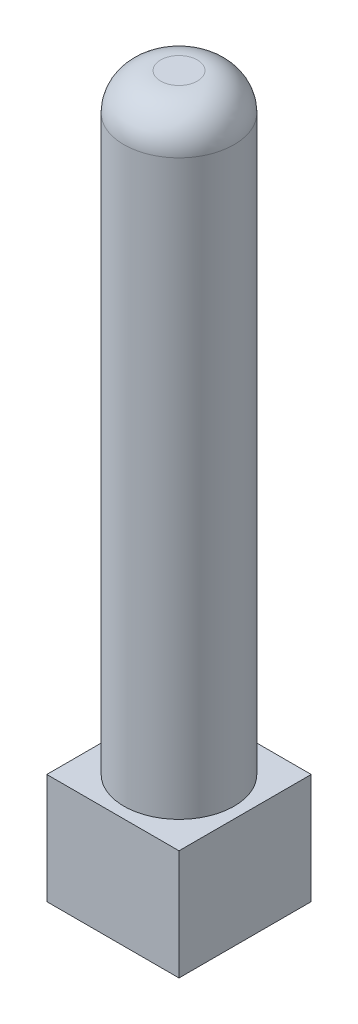
SolidWorks part; units mm, degrees
ref_plane "Plan de face" through (0, 0, 0) normal (0, 0, 1) x (1, 0, 0)
ref_plane "Plan de dessus" through (0, 0, 0) normal (0, 1, 0) x (1, 0, 0)
ref_plane "Plan de droite" through (0, 0, 0) normal (1, 0, 0) x (0, 0, -1)
sketch "Esquisse1" plane through (0, 0, 0) normal (0, 1, 0) x (1, 0, 0)
  circle A0 centre (0, 0) radius 1.5
extrude "Boss.-Extru.1" add sketch "Esquisse1" along normal blind 16.6
sketch "Esquisse2" plane through (0, 0, 0) normal (0, 0, 1) x (1, 0, 0)
  circle A0 centre (0, 13.6) radius 1
  dimension "D3" = 2
  dimension "D1" = 13.6
  dimension "D2" = 0
extrude "Enlèv. mat.-Extru.1" [suppressed] cut sketch "Esquisse2" against normal through all both and the other way through all
fillet "Congé1" [suppressed] radius 0.1
sketch "Esquisse3" plane through (0, 0, 0) normal (0, 1, 0) x (1, 0, 0)
  line L1 (1.8, 1.8) -> (-1.8, 1.8)
  line L2 (1.8, 1.8) -> (1.8, -1.8)
  line L3 (1.8, -1.8) -> (-1.8, -1.8)
  line L4 (-1.8, 1.8) -> (-1.8, -1.8)
  line L5 (1.8, 1.8) -> (-1.8, -1.8) construction
  line L6 (1.8, -1.8) -> (-1.8, 1.8) construction
  point P0 (0, 0)
  dimension "D1" = 1.8
  dimension "D2" = 1.8
extrude "Boss.-Extru.2" add sketch "Esquisse3" against normal blind 3
fillet "Congé2" radius 1 1 edges at (0, 16.6, 1.5) type face fillet first side face at (0, 16.6, 1.5) second side face at (0, 16.6, 1.5)
